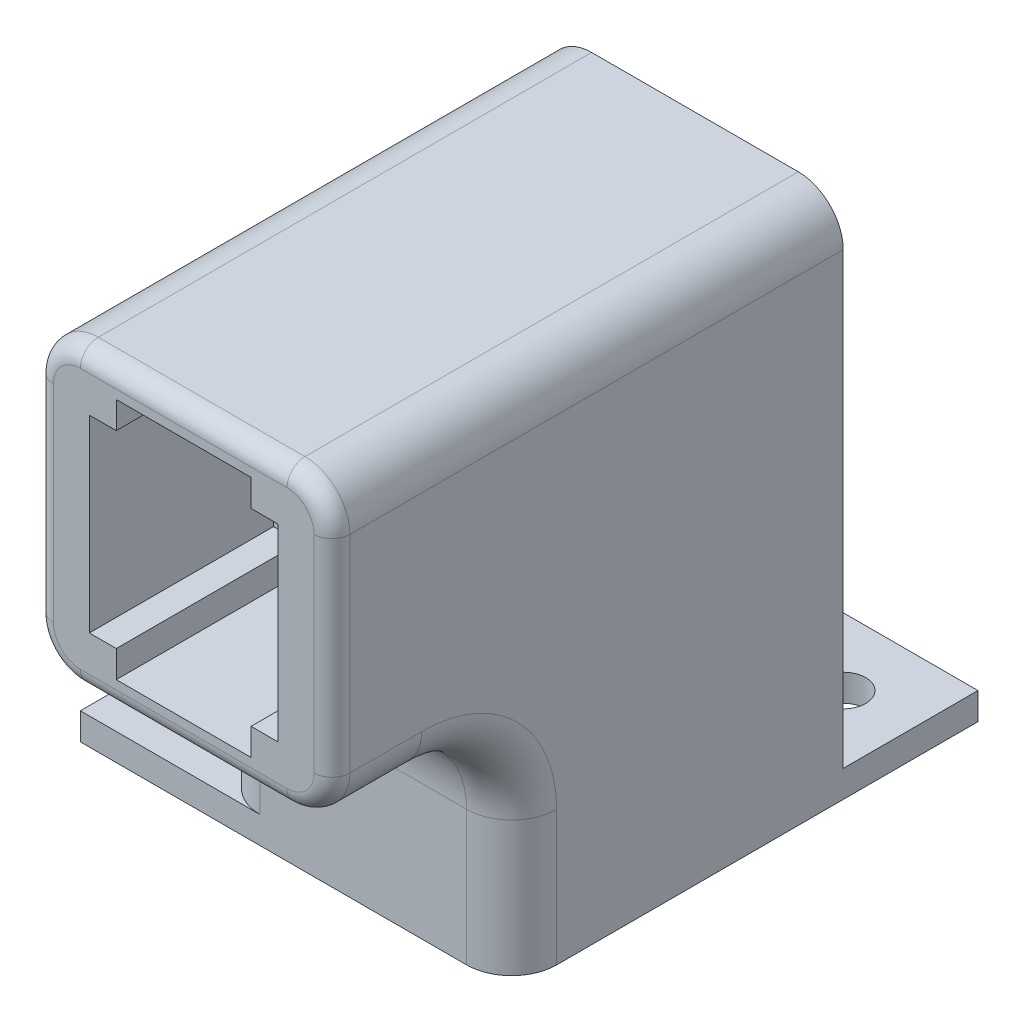
SolidWorks part; units mm, degrees
ref_plane "Alzado" through (0, 0, 0) normal (0, 0, 1) x (1, 0, 0)
ref_plane "Planta" through (0, 0, 0) normal (0, 1, 0) x (1, 0, 0)
ref_plane "Vista lateral" through (0, 0, 0) normal (1, 0, 0) x (0, 0, -1)
sketch "Sketch1" plane through (0, 0, 0) normal (0, 0, 1) x (1, 0, 0)
  line L1 (0, 0) -> (33, 0)
  line L2 (0, 0) -> (0, 33)
  line L3 (0, 33) -> (33, 33)
  line L4 (33, 0) -> (33, 33)
  dimension "D1" = 33
  dimension "D2" = 33
extrude "Boss-Extrude1" add sketch "Sketch1" along normal blind 20
shell "Shell1" thickness 6 removed face at (16.5, 16.5, 20)
sketch "Sketch2" plane through (0, 0, 0) normal (0, 0, -1) x (-1, 0, 0)
  line L2 (-33, 33) -> (0, 33)
  line L3 (-33, 33) -> (-33, -22)
  line L4 (-33, -22) -> (0, -22)
  line L5 (0, 33) -> (0, -22)
  dimension "D1" = 55
extrude "Boss-Extrude2" add sketch "Sketch2" along normal blind 36.9
sketch "Sketch5" plane through (0, -22, 0) normal (0, -1, 0) x (1, 0, 0)
  line L0 (0, -36.9) -> (0, 0) construction
  line L1 (-15, -51.9) -> (33, -51.9)
  line L2 (-15, -51.9) -> (-15, 0)
  line L3 (-15, 0) -> (33, 0)
  line L4 (33, -51.9) -> (33, 0)
  line L5 (-15, -51.9) -> (33, 0) construction
  line L6 (-15, 0) -> (33, -51.9) construction
  line L7 (33, -36.9) -> (0, -36.9) construction
  line L8 (33, -36.9) -> (33, 0) construction
  line L9 (33, 0) -> (0, 0) construction
  point P0 (9, -25.95)
  dimension "D1" = 15
  dimension "D2" = 15
extrude "Boss-Extrude3" add sketch "Sketch5" along normal blind 3
sketch "Sketch6" plane through (0, -22, 0) normal (0, 1, 0) x (1, 0, 0)
  line L0 (-15, 0) -> (0, 0) construction
  line L1 (-15, 0) -> (-15, 51.9) construction
  line L2 (-15, 0) -> (-15, 51.9) construction
  line L3 (-15, 51.9) -> (33, 51.9) construction
  line L4 (33, 51.9) -> (33, 36.9) construction
  circle A0 centre (-7.5, 7.5) radius 2.5
  circle A2 centre (-7.5, 44.4) radius 2.5
  circle A3 centre (25.5, 44.4) radius 2.5
  dimension "D1" = 5
  dimension "D2" = 7.5
  dimension "D3" = 5
  dimension "D4" = 7.5
  dimension "D7" = 5
  dimension "D5" = 7.5
  dimension "D6" = 7.5
  dimension "D8" = 7.5
  dimension "D9" = 7.5
ref_plane "Plane25" through (16.5, 0, 0) normal (-1, 0, 0) x (0, 0, 1)
extrude "Cut-Extrude1" cut sketch "Sketch6" against normal through all
sketch "Sketch7" plane through (0, 27, 0) normal (0, -1, 0) x (1, 0, 0)
  line L0 (27, 20) -> (6, 20) construction
  line L1 (9, 20) -> (24, 20)
  line L2 (9, 20) -> (9, -30)
  line L3 (9, -30) -> (24, -30)
  line L4 (24, 20) -> (24, -30)
  line L6 (0, 20) -> (0, 0) construction
  dimension "D1" = 15
  dimension "D2" = 9
  dimension "D3" = 50
extrude "Cut-Extrude2" cut sketch "Sketch7" against normal blind 3
ref_plane "Plane26" through (0, 16.5, 0) normal (0, -1, 0) x (-1, 0, 0)
mirror "Mirror2" about plane through (0, 16.5, 0) normal (0, -1, 0) of "Cut-Extrude2"
sketch "Sketch9" plane through (0, 0, 6) normal (0, 0, 1) x (1, 0, 0)
  line L1 (6, 27) -> (27, 27)
  line L2 (6, 27) -> (6, 6)
  line L3 (6, 6) -> (27, 6)
  line L4 (27, 27) -> (27, 6)
extrude "Cut-Extrude3" cut sketch "Sketch9" against normal blind 39
sketch "Sketch10" plane through (27, 0, 0) normal (-1, 0, 0) x (0, 0, 1)
  line L0 (0, 0) -> (0, 3.8) construction
  line L1 (0, 3.8) -> (-36.9, 3.8) construction
  line L2 (-36.9, -22) -> (-36.9, 33) construction
  line L3 (-36.9, 29.2) -> (0, 29.2) construction
  line L4 (0, 29.2) -> (0, 33) construction
  line L5 (-18.45, 29.2) -> (-18.45, 3.8) construction
  line L6 (20, 33) -> (-36.9, 33) construction
  line L7 (20, 33) -> (-36.9, 33) construction
  circle A0 centre (-18.45, 16.5) radius 5
  dimension "D3" = 10
  dimension "D1" = 3.8
  dimension "D2" = 3.8
extrude "Boss-Extrude4" add sketch "Sketch10" along normal blind 7.5
sketch "Sketch12" plane through (6, 0, 0) normal (1, 0, 0) x (0, 0, -1)
  line L0 (-20, 27) -> (33, 27) construction
  line L1 (33, 27) -> (5, 27)
  line L2 (33, 27) -> (33, 6)
  line L3 (33, 6) -> (5, 6)
  line L4 (5, 27) -> (5, 6)
  line L5 (33, 27) -> (33, 6) construction
  line L6 (-20, 6) -> (33, 6) construction
  dimension "D1" = 28
extrude "Cut-Extrude4" cut sketch "Sketch12" against normal blind 19
sketch "Sketch13" plane through (19.5, 0, 0) normal (-1, 0, 0) x (0, 0, 1)
  circle A0 centre (-18.45, 16.5) radius 2
  dimension "D1" = 4
extrude "Boss-Extrude5" add sketch "Sketch13" along normal up to surface (13.5 mm away)
fillet "Fillet1" radius 10 1 edges at (16.5, 0, 0)
sketch "Sketch14" plane through (0, 0, 20) normal (0, 0, 1) x (1, 0, 0)
  line L0 (9, 30) -> (9, 27) construction
  line L1 (6, 6) -> (9, 6)
  line L2 (6, 6) -> (6, 9)
  line L3 (6, 9) -> (9, 9)
  line L4 (9, 6) -> (9, 9)
  line L5 (6, 27) -> (9, 27)
  line L6 (6, 27) -> (6, 24)
  line L7 (6, 24) -> (9, 24)
  line L8 (9, 27) -> (9, 24)
  line L9 (27, 27) -> (24, 27)
  line L10 (27, 27) -> (27, 24)
  line L11 (27, 24) -> (24, 24)
  line L12 (24, 27) -> (24, 24)
  line L13 (27, 6) -> (24, 6)
  line L14 (27, 6) -> (27, 9)
  line L15 (27, 9) -> (24, 9)
  line L16 (24, 6) -> (24, 9)
  line L21 (24, 30) -> (24, 27) construction
  dimension "D1" = 3
extrude "Boss-Extrude6" add sketch "Sketch14" along normal blind 4.5 from surface at -25 starting at face at (3, 16.5, -5)
fillet "Fillet2" radius 2 4 edges at (16.5, 0, 20) (16.5, 33, 20) (0, 16.5, 20) (33, 16.5, 20)
fillet "Fillet3" radius 5 8 edges at (0, 16.5, -33) (0, 6, -19) (0, 16.5, -5) (0, 27, -19) (33, 33, -9.45) (0, 33, -9.45) (0.5858, 32.4142, 19.4142) (32.4142, 32.4142, 19.4142)
fillet "Fillet4" radius 5 8 edges at (0.5858, 0.5858, 19.4142) (32.4142, 0.5858, 19.4142) (33, 0, 14) (33, -17.5, 0) (0, -16, 0) (0, 0, 14) (33, -2.9289, 2.9289) (0, -2.9289, 2.9289)
